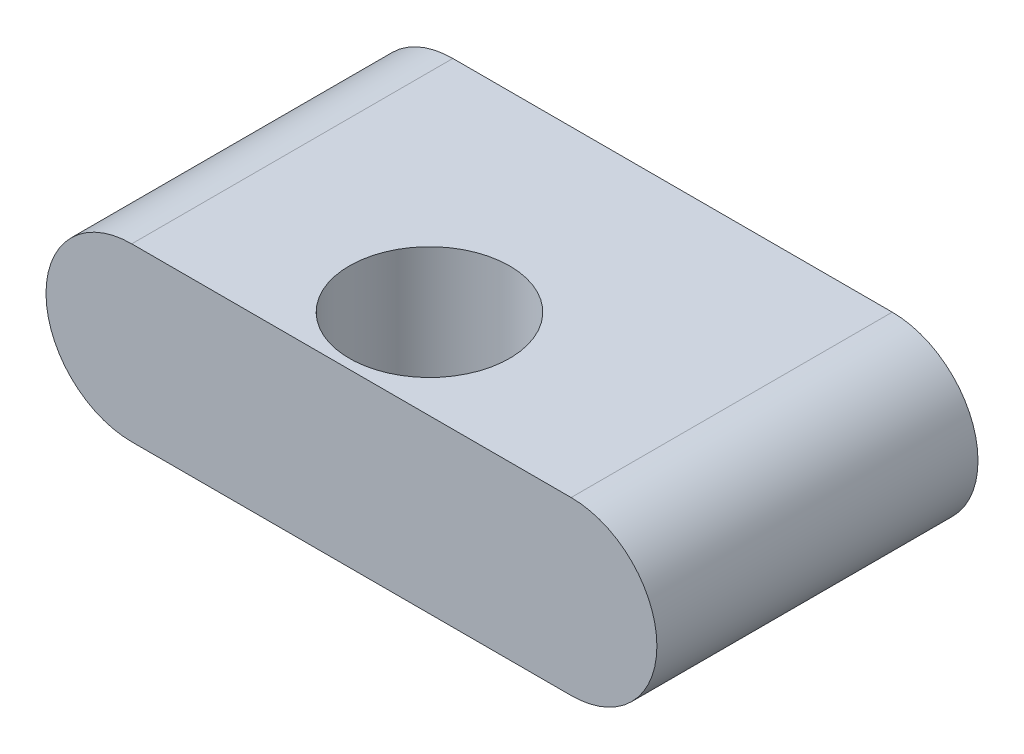
SolidWorks part; units mm, degrees
ref_plane "前视基准面" through (0, 0, 0) normal (0, 0, 1) x (1, 0, 0)
ref_plane "上视基准面" through (0, 0, 0) normal (0, 1, 0) x (1, 0, 0)
ref_plane "右视基准面" through (0, 0, 0) normal (1, 0, 0) x (0, 0, -1)
other "Configuration Table"
sketch "草图1" plane through (0, 0, 0) normal (0, 0, 1) x (1, 0, 0)
  line L0 (0, 0) -> (82.1043, 0) construction
  line L1 (0, 16.023) -> (82.1043, 16.023)
  line L2 (0, -16.023) -> (82.1043, -16.023)
  arc A0 (0, 16.023) -> (0, -16.023) centre (0, 0) ccw
  arc A1 (82.1043, -16.023) -> (82.1043, 16.023) centre (82.1043, 0) ccw
  point P3 (41.0521, 0)
extrude "凸台-拉伸1" add sketch "草图1" along normal blind 20 and the other way blind 20
sketch "草图2" plane through (0, 0, -20) normal (0, 0, -1) x (-1, 0, 0)
  line L2 (0, 16.023) -> (-82.1043, 16.023)
  line L3 (-82.1043, -16.023) -> (0, -16.023)
  line L4 (0, 16.023) -> (-82.1043, 16.023)
  line L5 (-82.1043, -16.023) -> (0, -16.023)
  arc A2 (0, -16.023) -> (0, 16.023) centre (0, 0) ccw
  arc A3 (-82.1043, 16.023) -> (-82.1043, -16.023) centre (-82.1043, 0) ccw
  arc A4 (0, -16.023) -> (0, 16.023) centre (0, 0) ccw
  arc A5 (-82.1043, 16.023) -> (-82.1043, -16.023) centre (-82.1043, 0) ccw
  dimension "D1" = 0
extrude "拉伸-薄壁1" add sketch "草图2" along normal blind 20 thin thin type one direction reverse wall 5
sketch "草图3" plane through (0, -16.023, 0) normal (0, -1, 0) x (1, 0, 0)
  circle A0 centre (38.8665, 3.2354) radius 14.9759
extrude "切除-拉伸1" cut sketch "草图3" against normal through all
